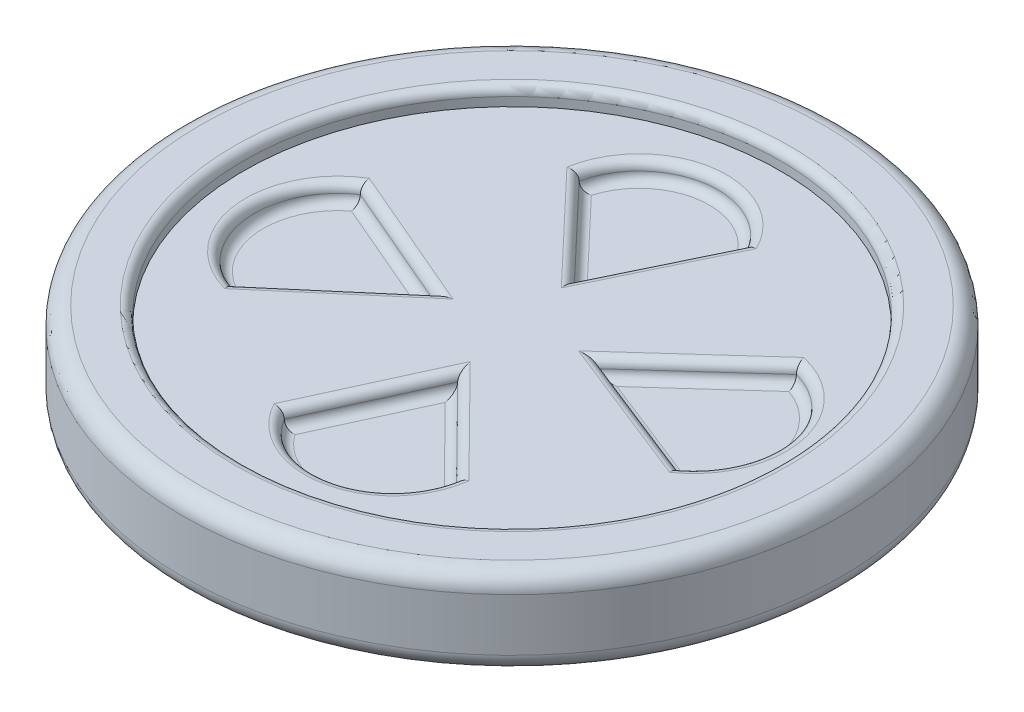
SolidWorks part; units mm, degrees
ref_plane "Front Plane" through (0, 0, 0) normal (0, 0, 1) x (1, 0, 0)
ref_plane "Top Plane" through (0, 0, 0) normal (0, 1, 0) x (1, 0, 0)
ref_plane "Right Plane" through (0, 0, 0) normal (1, 0, 0) x (0, 0, -1)
sketch "Sketch1" plane through (0, 0, 0) normal (0, 1, 0) x (1, 0, 0)
  circle A0 centre (-29.8779, 24.8828) radius 37.6304
extrude "Boss-Extrude1" add sketch "Sketch1" along normal blind 10
fillet "Fillet2" radius 2 1 edges at (-29.8779, 10, 12.7476)
fillet "Fillet3" radius 2 1 edges at (-29.8779, 0, 12.7476)
sketch "Sketch2" plane through (0, 10, 0) normal (0, 1, 0) x (1, 0, 0)
  circle A2 centre (-29.8779, 24.8828) radius 30.6304
  circle A3 centre (-29.8779, 24.8828) radius 30.6304
  dimension "D1" = 5
extrude "Cut-Extrude1" cut sketch "Sketch2" against normal blind 2 contours A3
fillet "Fillet4" radius 1 1 edges at (-29.8779, 10, 5.7476)
sketch "Sketch8" plane through (0, 8, 0) normal (0, 1, 0) x (1, 0, 0)
  line L0 (-34.7179, 55.1283) -> (-24.664, -5.3006)
  line L1 (-41.3413, 44.0134) -> (-31.0648, 33.1709)
  line L2 (-60.1379, 20.1338) -> (0.2896, 30.1874)
  line L3 (-24.6639, 46.4331) -> (-31.0648, 33.1709)
  line L4 (-18.0595, 6.7373) -> (-28.4097, 17.2125)
  line L5 (-34.622, 3.6267) -> (-28.4097, 17.2125)
  line L6 (-50.1857, 13.252) -> (-37.7479, 23.8589)
  line L7 (-52.5058, 30.1874) -> (-37.7479, 23.8589)
  line L8 (-9.8128, 37.2905) -> (-21.7265, 26.5245)
  line L9 (-6.5243, 20.5162) -> (-21.7265, 26.5245)
  arc A0 (-24.6639, 46.4331) -> (-41.3413, 44.0134) centre (-32.5438, 42.0604) ccw
  circle A1 centre (-29.8779, 24.8828) radius 30.6304 construction
  arc A2 (-18.0595, 6.7373) -> (-34.622, 3.6267) centre (-26.9307, 8.323) cw
  arc A3 (-52.5058, 30.1874) -> (-50.1857, 13.252) centre (-47.1549, 22.2938) ccw
  arc A4 (-9.8128, 37.2905) -> (-6.5243, 20.5162) centre (-12.3195, 28.0896) cw
  point P4 (-29.8779, 24.8828)
extrude "Cut-Extrude4" cut sketch "Sketch8" against normal blind 2 contours L5 L4 A2 | L3 L1 A0 | L9 L8 A4 | A3 L6 L7
fillet "Fillet5" radius 1 23 edges at (-45.1269, 6, -27.0232) (-27.8644, 6, -39.802) (-2.9614, 6, -29.9241) (-23.2346, 6, -11.9749) (-2.9614, 8, -29.9241) (-15.7696, 6, -31.9075) (-15.7696, 8, -31.9075) (-14.1254, 6, -23.5203) (-14.1254, 8, -23.5203) (-23.2346, 8, -11.9749) (-31.5158, 6, -10.4196) (-25.2673, 6, 0.5339) (-25.2673, 8, 0.5339) (-31.5158, 8, -10.4196) (-56.603, 6, -20.9995) (-33.8377, 6, -50.9788) (-36.203, 6, -38.5921) (-27.8644, 8, -39.802) (-33.8377, 8, -50.9788) (-36.203, 8, -38.5921) (-45.1269, 8, -27.0232) (-43.9668, 8, -18.5554) (-56.603, 8, -20.9995)
